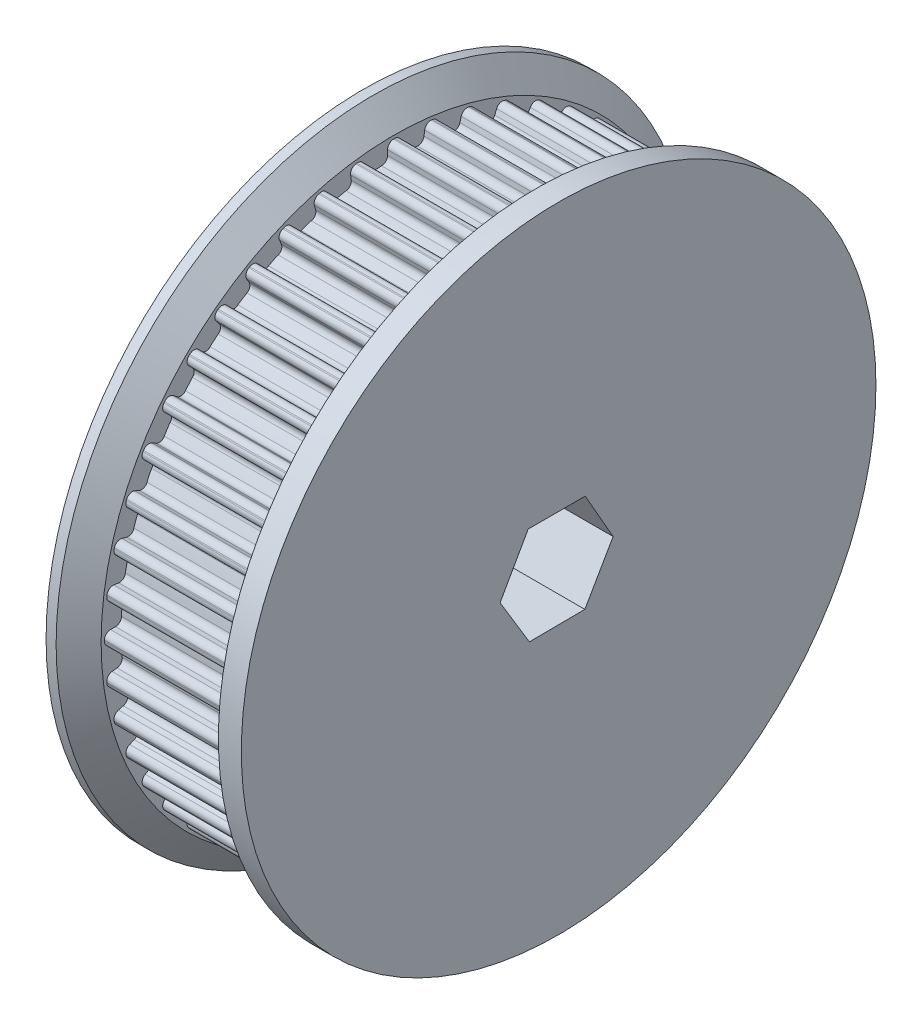
SolidWorks part; units mm, degrees
ref_plane "Front Plane" through (0, 0, 0) normal (0, 0, 1) x (1, 0, 0)
ref_plane "Top Plane" through (0, 0, 0) normal (0, 1, 0) x (1, 0, 0)
ref_plane "Right Plane" through (0, 0, 0) normal (1, 0, 0) x (0, 0, -1)
sketch "Sketch1" plane through (0, 0, 0) normal (1, 0, 0) x (0, 0, -1)
  circle A0 centre (0, 0) radius 35.695
  dimension "D1" = 71.39
extrude "Boss-Extrude1" add sketch "Sketch1" along normal blind 18.54 contours A0
sketch "Sketch8" plane through (18.54, 0, 0) normal (1, 0, 0) x (0, 0, -1)
  line L0 (1.5812, -1.8939) -> (0, 0) construction
  line L1 (0, 0) -> (0, 50.3807) construction
  line L2 (0, 37.9076) -> (0.875, 37.9076)
  line L3 (0.875, 37.9076) -> (0.875, 35.5476)
  line L4 (0.875, 35.5476) -> (-0.875, 35.5476)
  line L5 (-0.875, 35.5476) -> (-0.875, 37.9076)
  line L6 (-0.875, 37.9076) -> (0, 37.9076)
  point P8 (0, 0)
  point P10 (0.875, 33.4702)
  point P11 (0.1181, 37.4533)
  point P12 (-0.9106, 37.438)
  point P13 (-0.8552, 37.4584)
  point P14 (-0.9192, 37.4691)
  point P15 (0, 0)
  point P16 (0, 0)
  point P17 (0, 0)
  point P18 (-0.875, 33.783)
  point P19 (-0.9325, 37.4889)
  point P20 (0, 0)
  point P21 (0.875, 36.9076)
  dimension "D1" = 0.875
  dimension "D2" = 0.875
  dimension "D3" = 2.36
sketch "Sketch9" plane through (0, 0, 0) normal (-1, 0, 0) x (0, 0, 1)
  line L0 (-3.4711, 6.4445) -> (-7.1255, 0.0437)
  line L1 (-7.1255, 0.0437) -> (-3.4298, -6.3571)
  line L2 (-3.4298, -6.3571) -> (3.8268, -6.4097)
  line L3 (3.8268, -6.4097) -> (7.6559, -0.0635)
  line L4 (7.6559, -0.0635) -> (3.9818, 6.4445)
  line L5 (3.9818, 6.4445) -> (-3.4711, 6.4445)
extrude "Boss-Extrude6" add sketch "Sketch8" against normal blind 18.5
fillet "Fillet6" radius 0.8 4 edges at (9.29, 35.6843, -0.875) (9.29, 35.6843, 0.875) (9.29, 37.9076, -0.875) (9.29, 37.9076, 0.875)
pattern_circular "CirPattern6" count 48 every 7.5 about axis through (18.54, 0, 0) along (-1, 0, 0) of "Fillet6", "Boss-Extrude6"
sketch "Sketch10" plane through (18.54, 0, 0) normal (1, 0, 0) x (0, 0, -1)
  circle A0 centre (0, 0) radius 41.5
sketch "Sketch11" plane through (0, 0, 0) normal (-1, 0, 0) x (0, 0, 1)
  circle A0 centre (0, 0) radius 41.5
extrude "Boss-Extrude7" add sketch "Sketch10" along normal blind 3
extrude "Boss-Extrude8" add sketch "Sketch11" along normal blind 4
chamfer "Chamfer1" distance 3.2 angle 40 1 edges at (0, 0, 41.5) first distance on face at (0, 0, -35.695)
extrude "Cut-Extrude5" cut sketch "Sketch9" against normal through all both and the other way through all
